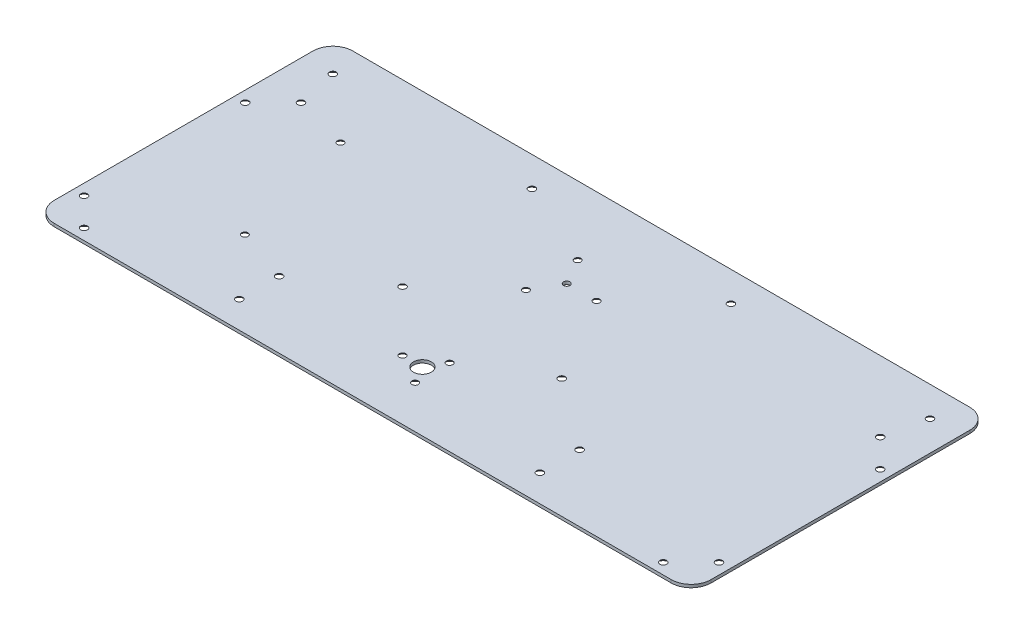
SolidWorks part; units mm, degrees
material "Alliage 1060"
ref_plane "Front" through (0, 0, 0) normal (0, 0, 1) x (1, 0, 0)
ref_plane "Top" through (0, 0, 0) normal (0, 1, 0) x (1, 0, 0)
ref_plane "Right" through (0, 0, 0) normal (1, 0, 0) x (0, 0, -1)
sketch "Esquisse1" plane through (0, 0, 0) normal (0, 1, 0) x (1, 0, 0)
  line L0 (0, 0) -> (0, 120) construction
  line L1 (-165, 120) -> (165, 120)
  line L2 (-165, 120) -> (-165, -30)
  line L3 (-165, -30) -> (165, -30)
  line L4 (165, 120) -> (165, -30)
  circle A0 centre (0, 0) radius 4.5
  dimension "D1" = 9
  dimension "D2" = 120
  dimension "D3" = 330
  dimension "D4" = 150
extrude "Boss.-Extru.1" add sketch "Esquisse1" along normal blind 1.5
hole_wizard "Fraisage pour vis à tête fraisée M31" positions "Esquisse2" profile "Esquisse3" countersink size "M3" standard "ISO" end condition through all
sketch "Esquisse2" plane through (0, 0, 0) normal (0, -1, 0) x (-1, 0, 0)
  circle A0 centre (0, 0) radius 10 construction
  point P0 (-5, 8.6603)
  point P2 (-5, -8.6603)
  point P4 (10, 0)
  dimension "D1" = 120
  dimension "D2" = 20
sketch "Esquisse3" plane through (5, 0, -8.6603) normal (1, 0, 0) x (0, 0, -1)
  line L0 (0, 0) -> (0, 1.5)
  line L1 (0, 1.5) -> (1.6, 1.5)
  line L2 (1.6, 1.5) -> (1.6, 1.4)
  line L3 (1.6, 1.4) -> (3, 0)
  line L5 (3, 0) -> (0, 0)
  line L6 (-1.6, 1.4) -> (-3, 0) construction
  line L11 (0, -6.35) -> (0, 107.95) construction
  dimension "Diamètre du perçage jusqu'au prochain" = 3.2
  dimension "Profondeur du perçage jusqu'au prochain" = 1.5
  dimension "Diamètre du fraisage entrant" = 6
  dimension "Angle du fraisage entrant" = 90
fillet "Congé2" radius 10 4 edges at (165, 0.75, -120) (165, 0.75, 30) (-165, 0.75, 30) (-165, 0.75, -120)
sketch "Esquisse4" plane through (0, 1.5, 0) normal (0, 1, 0) x (1, 0, 0)
  line L0 (0, 0) -> (0, 72.5) construction
  line L1 (0, 72.5) -> (-110.2142, 45.0205) construction
  line L2 (-102.2307, 13.0008) -> (-118.1976, 77.0403) construction
  line L3 (155, 120) -> (-155, 120) construction
  line L4 (-7.5, 85.4904) -> (-7.5, 59.5096) construction
  line L5 (-7.5, 59.5096) -> (15, 72.5) construction
  line L6 (15, 72.5) -> (-7.5, 85.4904) construction
  line L7 (2.0339, 50.313) -> (-99.9178, 40.9669) construction
  line L8 (-8.6203, 93.0448) -> (-103.0261, 53.4335) construction
  circle A0 centre (-102.2307, 13.0008) radius 1.6
  circle A1 centre (-118.1976, 77.0403) radius 1.6
  arc A2 (2.0339, 50.313) -> (-8.6203, 93.0448) centre (0, 72.5) ccw construction
  circle A3 centre (5, 8.6603) radius 1.6 construction
  circle A4 centre (0, 72.5) radius 7.5 construction
  circle A5 centre (15, 72.5) radius 1.6
  circle A6 centre (-7.5, 85.4904) radius 1.6
  circle A7 centre (-7.5, 59.5096) radius 1.6
  arc A9 (-103.0261, 53.4335) -> (-99.9178, 40.9669) centre (-100.5112, 47.4397) ccw construction
  circle A10 centre (0, 72.5) radius 1.6
  point P7 (-110.2142, 45.0205)
  dimension "D6" = 44.56
  dimension "D7" = 300
  dimension "D2" = 10
  dimension "D8" = 6.5
  dimension "D1" = 47.5
  dimension "D3" = 66
  dimension "D4" = 76
  dimension "D5" = 15
extrude "Enlèv. mat.-Extru.1" cut sketch "Esquisse4" against normal through all
chamfer "Chanfrein1" distance 1.4 angle 45 5 edges at (-118.1976, 0, -75.4403) (-102.2307, 0, -11.4008) (-7.5, 0, -57.9096) (-7.5, 0, -83.8904) (15, 0, -70.9)
hole_wizard "Fraisage pour vis à tête fraisée M32" positions "Esquisse5" profile "Esquisse6" countersink size "M3" standard "Ansi Metric" end condition through all
sketch "Esquisse5" plane through (0, 0, 0) normal (0, -1, 0) x (-1, 0, 0)
  line L0 (0, 50) -> (0, -50) construction
  line L1 (-75.5, 3.5) -> (-75.5, -16.5) construction
  line L3 (155, -30) -> (-155, -30) construction
  line L4 (-165, -20) -> (-165, 110) construction
  line L5 (-145.5, -24.5) -> (-145.5, -30) construction
  line L7 (-159.5, -10.5) -> (-165, -10.5) construction
  line L9 (-159.5, 70.5) -> (-165, 70.5) construction
  line L11 (-145.5, 84.5) -> (-145.5, 90) construction
  line L12 (-159.5, -10.5) -> (-145.5, -24.5) construction
  line L14 (-159.5, 70.5) -> (-145.5, 84.5) construction
  line L16 (-150, 105) -> (-50, 105) construction
  line L18 (-155, 120) -> (155, 120) construction
  point P0 (-75.5, 3.5)
  point P2 (-75.5, -16.5)
  point P8 (75.5, -16.5)
  point P9 (75.5, 3.5)
  point P20 (-159.5, -10.5)
  point P22 (-145.5, -24.5)
  point P24 (-159.5, 70.5)
  point P26 (-145.5, 84.5)
  point P47 (-145.5, -27.25)
  point P59 (145.5, -24.5)
  point P60 (159.5, -10.5)
  point P61 (145.5, 84.5)
  point P62 (159.5, 70.5)
  point P63 (-150, 105)
  point P64 (-50, 105)
  point P81 (-40, 30)
  point P87 (40, 30)
  point P88 (50, 105)
  point P89 (150, 105)
  point P90 (271.3745, -83.4974)
  dimension "D1" = 20
  dimension "D2" = 13.5
  dimension "D3" = 89.5
  dimension "D4" = 5.5
  dimension "D5" = 19.5
  dimension "D6" = 135
  dimension "D7" = 120
  dimension "D8" = 100
  dimension "D9" = 15
  dimension "D10" = 15
  dimension "D11" = 90
  dimension "D12" = 125
sketch "Esquisse6" plane through (75.5, 0, -3.5) normal (1, 0, 0) x (0, 0, -1)
  line L0 (0, 0) -> (0, 1.5)
  line L1 (0, 1.5) -> (1.7, 1.5)
  line L2 (1.7, 1.5) -> (1.7, 1.45)
  line L3 (1.7, 1.45) -> (3.15, 0)
  line L5 (3.15, 0) -> (0, 0)
  line L6 (-1.7, 1.45) -> (-3.15, 0) construction
  line L11 (0, -6.35) -> (0, 107.95) construction
  dimension "Diamètre du perçage jusqu'au prochain" = 3.4
  dimension "Profondeur du perçage jusqu'au prochain" = 1.5
  dimension "Diamètre du fraisage entrant" = 6.3
  dimension "Angle du fraisage entrant" = 90
